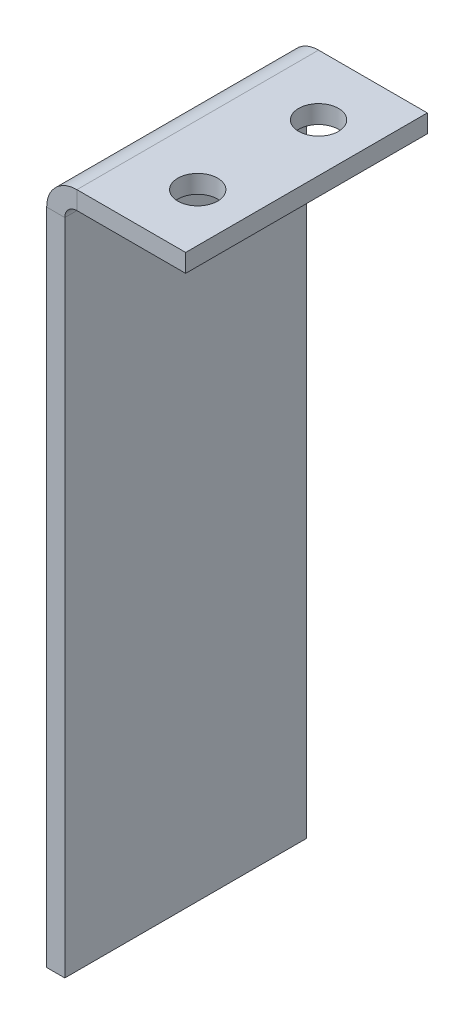
SolidWorks part; units mm, degrees
note: The reader was unsure of these and kept them because the rebuilt part matched: bend radius of "基体折弯2".
material "304单面拉丝"
ref_plane "前视" through (0, 0, 0) normal (0, 0, 1) x (1, 0, 0)
ref_plane "上视" through (0, 0, 0) normal (0, 1, 0) x (1, 0, 0)
ref_plane "右视" through (0, 0, 0) normal (1, 0, 0) x (0, 0, -1)
sketch "草图1" plane through (0, 0, 0) normal (0, 0, 1) x (1, 0, 0)
  line L0 (0, 0) -> (-10, 0)
  line L1 (-10, 0) -> (-10, -55.5)
  dimension "D1" = 10
  dimension "D2" = 55.5
sheet metal parameters "钣金1" thickness 1.5 parameters "D1"=1
base flange "基体-法兰1" sketch "草图1" end condition mid plane depth 20 reverse direction no thickness 1.5 reverse thickness direction no bend radius 1
bend "基体折弯2" bend radius 1 bend angle 90 parameters "D5"=2
hole_wizard "M4 螺纹孔1" positions "草图5" profile "草图4" tap size "M4" standard "Gb" end condition up to next
sketch "草图5" plane through (0, 1.5, 0) normal (0, 1, 0) x (1, 0, 0)
  line L0 (0, 0) -> (-22.3616, 0) construction
  line L2 (0, -10) -> (0, 10) construction
  point P0 (-4, 5)
  point P8 (-4, -5)
  dimension "D1" = 10
  dimension "D2" = 4
sketch "草图4" plane through (-4, 1.5, -5) normal (1, 0, 0) x (0, 0, 1)
  line L0 (0, 0) -> (0, 1.5)
  line L1 (0, 1.5) -> (1.65, 1.5)
  line L2 (1.65, 1.5) -> (1.65, 0)
  line L5 (1.65, 0) -> (0, 0)
  line L11 (0, -6.35) -> (0, 107.95) construction
  dimension "通孔螺纹孔钻头直径" = 3.3
  dimension "通孔螺纹孔钻头深度" = 1.5
cosmetic thread "孔螺蚊线1"
cosmetic thread "孔螺蚊线2"
flat pattern "平板型式1" [suppressed]
sketch "折弯-线1" plane through (-12, 0, 0) normal (1, 0, 0) x (0, 0, -1)
  line L0 (-15, 0.3744) -> (15, 0.3744) construction
  line L2 (-15, 0.3744) -> (15, 0.3744) construction
sketch3d "边界框1" [suppressed]
  line L0 (30, -40.7489, 0) -> (30, 12.7489, 0) construction
  line L1 (0, -40.7489, 0) -> (0, 12.7489, 0) construction
  line L2 (30, -40.7489, 0) -> (0, -40.7489, 0) construction
  line L3 (30, 12.7489, 0) -> (0, 12.7489, 0) construction
bend of the flat pattern "展开-<基体折弯2>1"
